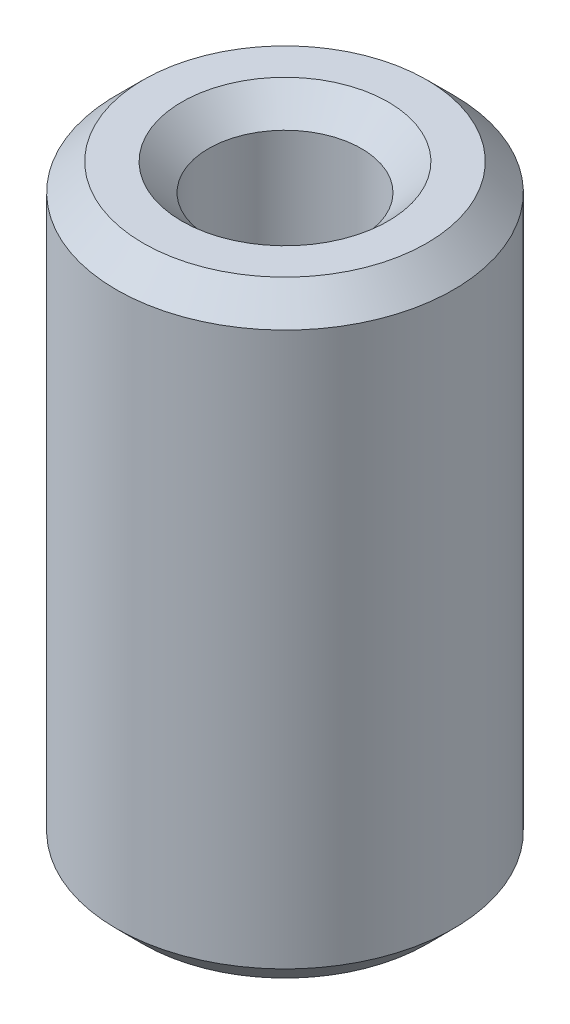
SolidWorks part; units mm, degrees
ref_plane "Front Plane" through (0, 0, 0) normal (0, 0, 1) x (1, 0, 0)
ref_plane "Top Plane" through (0, 0, 0) normal (0, 1, 0) x (1, 0, 0)
ref_plane "Right Plane" through (0, 0, 0) normal (1, 0, 0) x (0, 0, -1)
sketch "Sketch1" plane through (0, 0, 0) normal (0, 1, 0) x (1, 0, 0)
  circle A0 centre (0, 0) radius 22.5
  dimension "SLEEVE_OD" = 45
extrude "Boss-Extrude1" add sketch "Sketch1" along normal blind 81.0309
sketch "Sketch2" plane through (0, 0, 0) normal (0, 1, 0) x (1, 0, 0)
  circle A0 centre (0, 0) radius 10.1992
  dimension "BORE_D" = 20.3983
extrude "Cut-Extrude1" cut sketch "Sketch2" along normal through all
chamfer "Chamfer1" distance 3.5802 angle 45.08 4 edges at (0, 81.0309, 10.1992) (0, 0, 10.1992) (0, 0, 22.5) (0, 81.0309, 22.5) first distance on face at (0, 81.0309, 10.1992) first distance on face at (0, 0, 10.1992) first distance on face at (0, 81.0309, 22.5)
